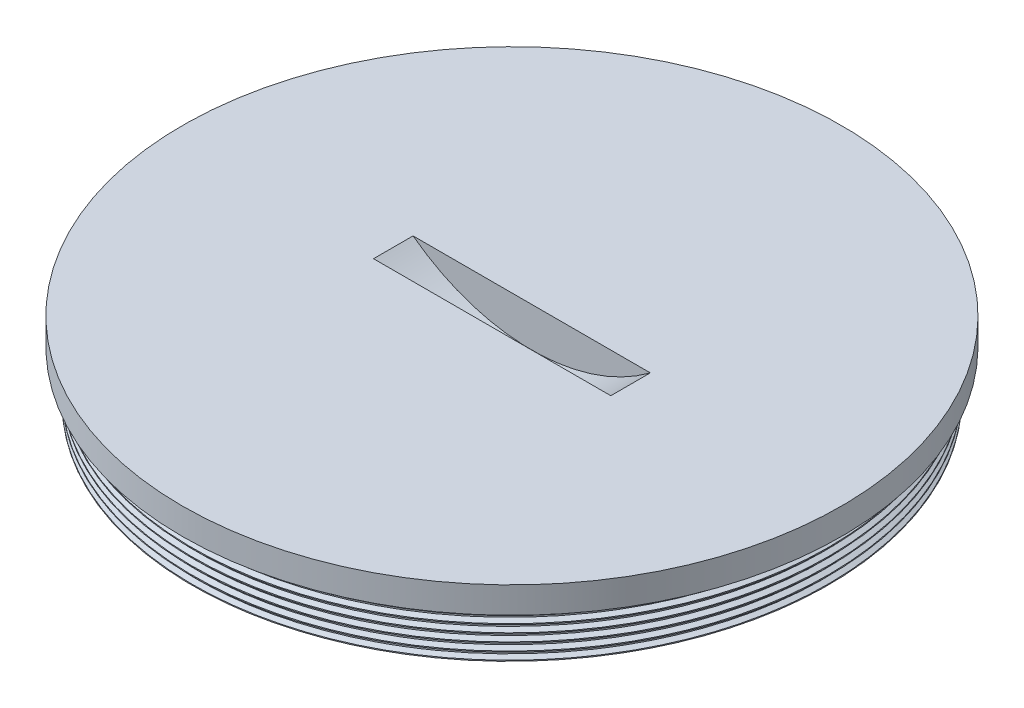
SolidWorks part; units mm, degrees
ref_plane "Front Plane" through (0, 0, 0) normal (0, 0, 1) x (1, 0, 0)
ref_plane "Top Plane" through (0, 0, 0) normal (0, 1, 0) x (1, 0, 0)
ref_plane "Right Plane" through (0, 0, 0) normal (1, 0, 0) x (0, 0, -1)
sketch "Sketch1" plane through (0, 0, 0) normal (0, 1, 0) x (1, 0, 0)
  circle A0 centre (0, 0) radius 23.8
  dimension "D1" = 47.6
extrude "Boss-Extrude1" add sketch "Sketch1" along normal blind 12.7
thread "MinColWidth_OnTracking1" pitch 0.6 method extrude profile "HeaderRowsCount1" start angle 0, offset 0, length 12.7, pitch 0.6, diameter 47.6
ref_plane "Plane1" through (-23.8, 12.7, 0) normal (0, 0, 1) x (-1, 0, 0)
sketch "HeaderRowsCount1" plane through (-23.8, 12.7, 0) normal (0, 0, 1) x (-1, 0, 0)
  line L0 (0, 0) -> (0, 0.6) construction
  line L1 (0, 0) -> (0.3248, 0.1875)
  line L2 (0.3248, 0.1875) -> (0.3248, 0.2625)
  line L3 (0.3248, 0.2625) -> (0, 0.45)
  line L4 (0.3248, 0.225) -> (0, 0.225) construction
  line L11 (0, 0) -> (0, 0.45)
  point P2 (0, 0)
  dimension "Pitch" = 0.6
  dimension "Profile_Angle" = 60
  dimension "Profile_Land" = 0.075
  dimension "Profile_Height" = 0.3248
sketch "Sketch2" plane through (0, 0, 0) normal (0, 0, 1) x (1, 0, 0)
  line L0 (0, 0) -> (0, 19.0669) construction
  line L1 (-25, 7.905) -> (25, 7.905)
  line L2 (-25, 7.905) -> (-25, 4.095)
  line L3 (-25, 4.095) -> (25, 4.095)
  line L4 (25, 7.905) -> (25, 4.095)
  line L5 (-25, 7.905) -> (25, 4.095) construction
  line L6 (-25, 4.095) -> (25, 7.905) construction
  point P0 (0, 6)
  dimension "D1" = 50
  dimension "D2" = 3.81
  dimension "D3" = 6
extrude "Cut-Extrude2" cut sketch "Sketch2" against normal through all both and the other way through all flip side to cut
sketch "Sketch3" plane through (0, 7.905, 0) normal (0, 1, 0) x (1, 0, 0)
  circle A0 centre (0, 0) radius 25
  dimension "D1" = 50
extrude "Boss-Extrude2" add sketch "Sketch3" along normal blind 2
sketch "Sketch4" plane through (0, 0, 0) normal (0, 0, 1) x (1, 0, 0)
  line L0 (25, 9.905) -> (-25, 9.905) construction
  line L1 (-9, 9.905) -> (9, 9.905)
  arc A0 (-9, 9.905) -> (9, 9.905) centre (0, 21.905) ccw
  dimension "D1" = 15
  dimension "D2" = 12
extrude "Cut-Extrude3" cut sketch "Sketch4" against normal blind 1.5 and the other way blind 1.5
